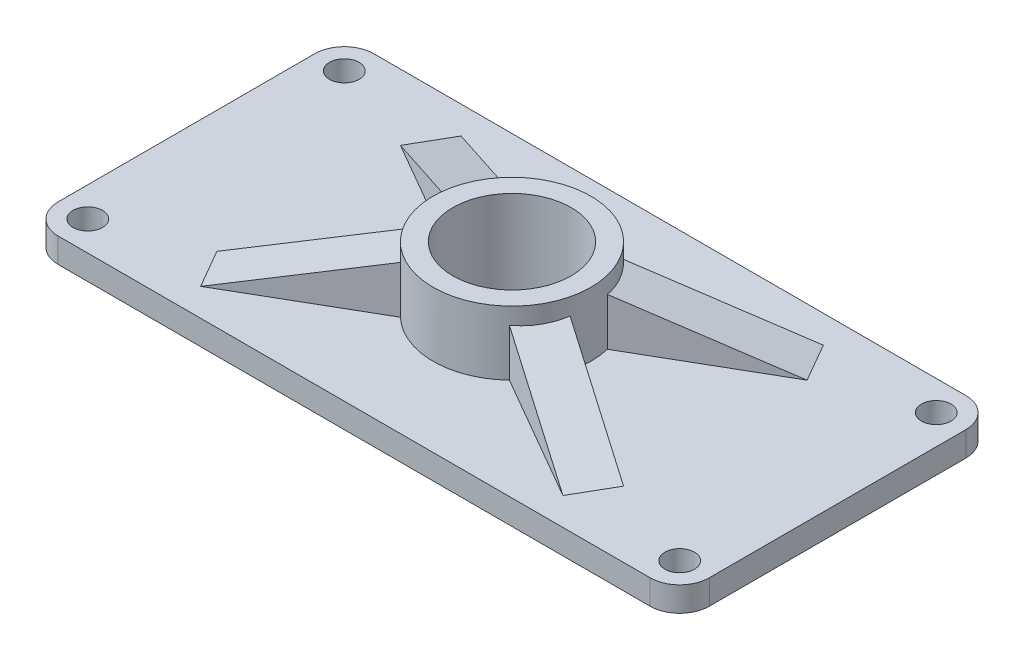
SolidWorks part; units mm, degrees
material "Thornel Mat VMA"
ref_plane "Front Plane" through (0, 0, 0) normal (0, 0, 1) x (1, 0, 0)
ref_plane "Top Plane" through (0, 0, 0) normal (0, 1, 0) x (1, 0, 0)
ref_plane "Right Plane" through (0, 0, 0) normal (1, 0, 0) x (0, 0, -1)
sketch "Sketch1" plane through (0, 0, 0) normal (0, 1, 0) x (1, 0, 0)
  line L1 (-60, 32) -> (60, 32)
  line L2 (-66, 26) -> (-66, -26)
  line L3 (-60, -32) -> (60, -32)
  line L4 (66, 26) -> (66, -26)
  line L5 (-66, 32) -> (66, -32) construction
  line L6 (-66, -32) -> (66, 32) construction
  circle A0 centre (-60, 26) radius 3
  arc A1 (-66, -26) -> (-60, -32) centre (-60, -26) ccw
  arc A2 (60, -32) -> (66, -26) centre (60, -26) ccw
  arc A3 (60, 32) -> (66, 26) centre (60, 26) cw
  arc A4 (-60, 32) -> (-66, 26) centre (-60, 26) ccw
  circle A5 centre (60, 26) radius 3
  circle A6 centre (60, -26) radius 3
  circle A7 centre (-60, -26) radius 3
  circle A8 centre (0, 0) radius 12
  circle A9 centre (0, 0) radius 16
  point P0 (0, 0)
  dimension "D3" = 6
  dimension "D4" = 6
  dimension "D5" = 32
  dimension "D6" = 24
  dimension "D1" = 132
  dimension "D2" = 64
extrude "Boss-Extrude1" add sketch "Sketch1" along normal blind 5 contours L1 A4 L2 A1 L3 A2 L4 A3 A9 A7 A6 A5 A0 region at (0, 0, -30.533)
extrude "Boss-Extrude2" add sketch "Sketch1<3>" along normal blind 18 contours A9 A8 region at (-15.5475, 0, 0)
sketch "Sketch1<3>" plane through (0, 0, 0) normal (0, 1, 0) x (1, 0, 0) same geometry as "Sketch1"
ref_axis "Axis1" through (0, 18, 0) along (0, -1, 0)
ref_plane "Plane1" through (0, 0, 0) normal (-0.5, 0, -0.866) x (0, -1, 0)
sketch "Sketch2" plane through (0, 0, 0) normal (-0.5, 0, -0.866) x (0, -1, 0)
  line L0 (-5, 12) -> (-5, 45)
  line L1 (-5, 35.9615) -> (-5, -67.9615) construction
  line L2 (-5, 44.1577) -> (-5, 70.1577) construction
  line L3 (-5, 45) -> (-15.7223, 12)
  line L4 (-15.7223, 12) -> (-5, 12)
  line L5 (-18, 0) -> (0, 0) construction
  line L6 (0, 0) -> (-40.0693, 0) construction
  line L7 (-15.7223, -12) -> (-5, -12)
  line L8 (-5, -45) -> (-15.7223, -12)
  line L9 (-5, -12) -> (-5, -45)
  dimension "D1" = 162
  dimension "D2" = 45
  dimension "D3" = 12
extrude "Boss-Extrude3" add sketch "Sketch2" along normal mid plane 9
mirror "Mirror1" about plane through (0, 0, 0) normal (0, 0, 1) of "Boss-Extrude3"
